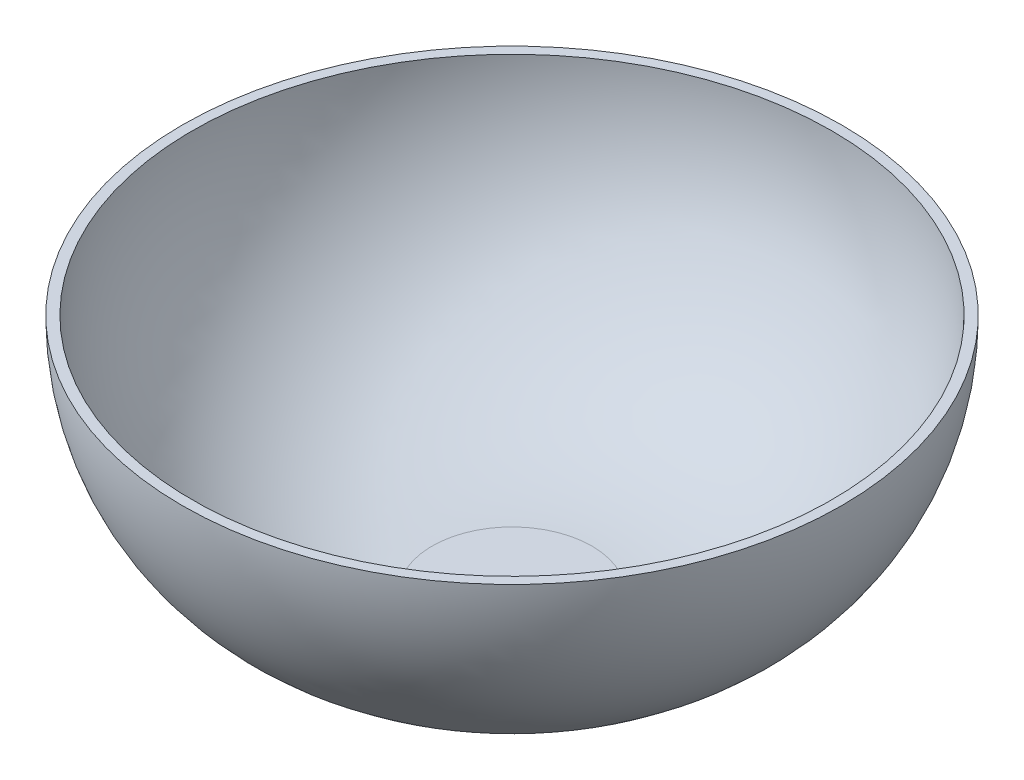
SolidWorks part; units mm, degrees
material "Maple"
ref_plane "Front Plane" through (0, 0, 0) normal (0, 0, 1) x (1, 0, 0)
ref_plane "Top Plane" through (0, 0, 0) normal (0, 1, 0) x (1, 0, 0)
ref_plane "Right Plane" through (0, 0, 0) normal (1, 0, 0) x (0, 0, -1)
sketch "Sketch1" plane through (0, 0, 0) normal (0, 0, 1) x (1, 0, 0)
  line L0 (203.2, 158.75) -> (209.55, 158.75)
  line L1 (0, 0) -> (50.8, 0)
  line L2 (0, 0) -> (0, 6.35)
  line L3 (0, 6.35) -> (50.8, 6.35)
  line L4 (50.8, 0) -> (50.8, 6.35)
  line L5 (209.55, 158.75) -> (209.55, 82.8099) construction
  arc A0 (50.8, 6.35) -> (203.2, 158.75) centre (50.8, 158.75) ccw
  arc A1 (50.8, 0) -> (209.55, 158.75) centre (50.8, 158.75) ccw
  point P7 (66.3745, 46.0162)
  point P10 (95.6591, 70.2591)
  dimension "D1" = 6.35
  dimension "D2" = 6.35
  dimension "D3" = 50.8
  dimension "D4" = 152.4
revolve "Revolve1" add sketch "Sketch1" angle 360 about L2 region at (206.375, 156.5049, 0) region at (25.4, 3.175, 0)
sketch "Sketch2" plane through (0, 0, 0) normal (0, -1, 0) x (1, 0, 0)
  circle A0 centre (0, 0) radius 6.35
  dimension "D1" = 12.7
extrude "Cut-Extrude1" cut sketch "Sketch2" against normal blind 4.826
